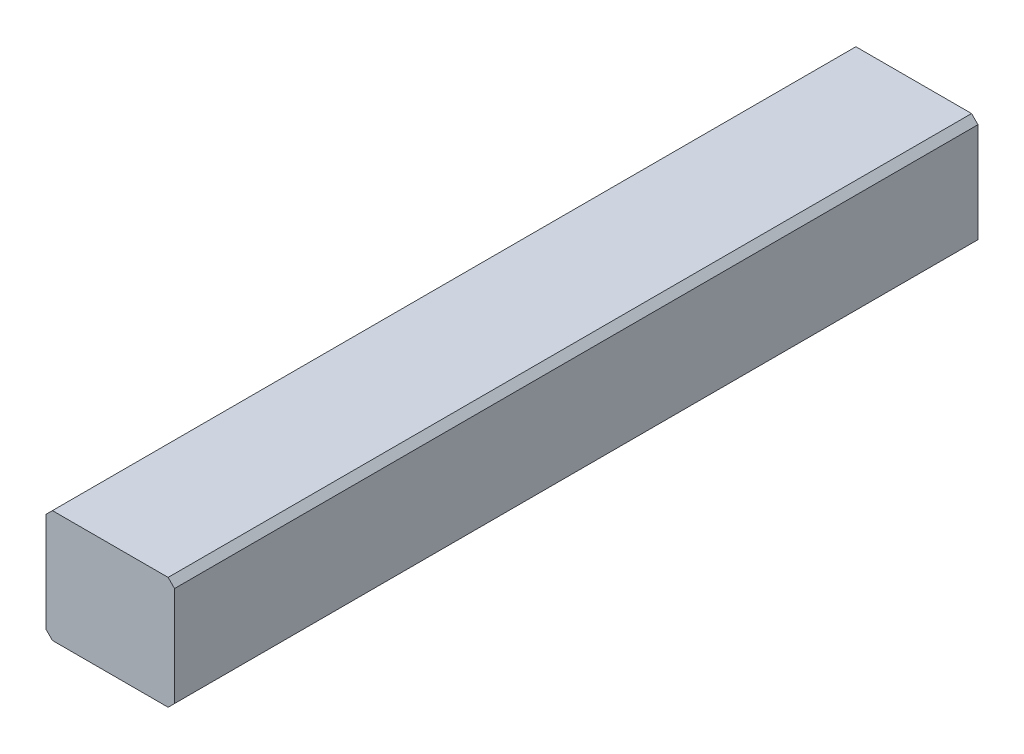
SolidWorks part; units mm, degrees
ref_plane "Front" through (0, 0, 0) normal (0, 0, 1) x (1, 0, 0)
ref_plane "Top" through (0, 0, 0) normal (0, 1, 0) x (1, 0, 0)
ref_plane "Right" through (0, 0, 0) normal (1, 0, 0) x (0, 0, -1)
sketch "body" plane through (0, 0, 0) normal (0, 0, 1) x (1, 0, 0)
  line L1 (0, 0) -> (8, 0)
  line L2 (0, 0) -> (0, 7)
  line L3 (0, 7) -> (8, 7)
  line L4 (8, 0) -> (8, 7)
  dimension "Thickness" = 7
  dimension "Width" = 8
extrude "Extrude1" add sketch "body" along normal blind 50
chamfer "Chamfer1" distance 0.4 4 edges at (0, 0, 25) (8, 0, 25) (0, 7, 25) (8, 7, 25)
